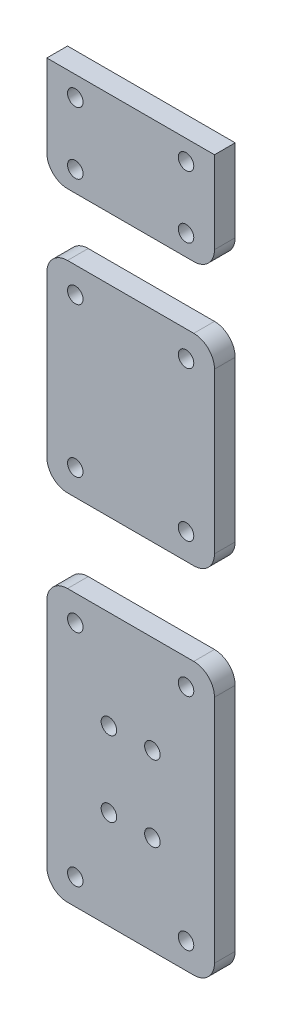
SolidWorks part; units mm, degrees
ref_plane "Front Plane" through (0, 0, 0) normal (0, 0, 1) x (1, 0, 0)
ref_plane "Top Plane" through (0, 0, 0) normal (0, 1, 0) x (1, 0, 0)
ref_plane "Right Plane" through (0, 0, 0) normal (1, 0, 0) x (0, 0, -1)
sketch "Sketch3" plane through (0, 0, 0) normal (0, 0, 1) x (1, 0, 0)
  line L0 (0, 94.0064) -> (0, 86.0614)
  line L1 (16.2, 94.0064) -> (16.2, 86.0614)
  line L2 (0, -0.1536) -> (16.2, -0.1536) construction
  line L3 (0, 76.0614) -> (0, 60.6064)
  line L4 (0, 94.0064) -> (16.2, 94.0064)
  line L5 (0, 12.3464) -> (4, 12.3464) construction
  line L6 (2, 58.6064) -> (4, 58.6064)
  line L7 (16.2, 76.0614) -> (16.2, 60.6064)
  line L8 (0, 48.6064) -> (0, 26.3464)
  line L9 (16.2, 48.6064) -> (16.2, 26.3464)
  line L10 (16.2, 12.3464) -> (16.2, -0.1536) construction
  line L11 (0, 12.3464) -> (0, -0.1536) construction
  line L12 (6, 12.3464) -> (6, 24.3464)
  line L13 (6, 24.3464) -> (10.2, 24.3464)
  line L14 (4, 12.3464) -> (4, 24.3464)
  line L15 (6, 12.3464) -> (10.2, 12.3464) construction
  line L16 (4, 50.6064) -> (4, 58.6064)
  line L17 (4, 78.0614) -> (4, 84.0614)
  line L18 (6, 50.6064) -> (6, 58.6064)
  line L19 (6, 78.0614) -> (6, 84.0614)
  line L20 (6, 84.0614) -> (10.2, 84.0614)
  line L21 (6, 78.0614) -> (10.2, 78.0614)
  line L22 (6, 58.6064) -> (10.2, 58.6064)
  line L23 (6, 50.6064) -> (10.2, 50.6064)
  line L24 (8.1, 94.0064) -> (8.1, -0.1536) construction
  line L25 (12.2, 50.6064) -> (12.2, 58.6064)
  line L26 (2, 50.6064) -> (4, 50.6064)
  line L27 (2, 24.3464) -> (4, 24.3464)
  line L28 (10.2, 12.3464) -> (10.2, 24.3464)
  line L29 (12.2, 12.3464) -> (12.2, 24.3464)
  line L30 (2, 78.0614) -> (4, 78.0614)
  line L31 (10.2, 50.6064) -> (10.2, 58.6064)
  line L32 (2, 84.0614) -> (4, 84.0614)
  line L33 (12.2, 78.0614) -> (12.2, 84.0614)
  line L34 (10.2, 78.0614) -> (10.2, 84.0614)
  line L35 (12.2, 84.0614) -> (14.2, 84.0614)
  line L36 (12.2, 78.0614) -> (14.2, 78.0614)
  line L37 (12.2, 58.6064) -> (14.2, 58.6064)
  line L38 (12.2, 50.6064) -> (14.2, 50.6064)
  line L39 (12.2, 12.3464) -> (16.2, 12.3464) construction
  line L40 (12.2, 24.3464) -> (14.2, 24.3464)
  line L41 (4, 12.3464) -> (6, 12.3464)
  line L42 (10.2, 12.3464) -> (12.2, 12.3464)
  circle A0 centre (6, 33.8464) radius 0.75
  circle A1 centre (10.2, 33.8464) radius 0.75
  circle A2 centre (2.75, 86.0614) radius 0.75
  circle A3 centre (10.2, 41.1664) radius 0.75
  circle A4 centre (13.45, 48.1064) radius 0.75
  circle A5 centre (2.75, 92.0614) radius 0.75
  circle A6 centre (13.45, 86.0614) radius 0.75
  circle A7 centre (2.75, 61.1064) radius 0.75
  arc A8 (14.2, 24.3464) -> (16.2, 26.3464) centre (14.2, 26.3464) ccw
  arc A9 (16.2, 48.6064) -> (14.2, 50.6064) centre (14.2, 48.6064) ccw
  arc A10 (2, 50.6064) -> (0, 48.6064) centre (2, 48.6064) ccw
  arc A11 (0, 26.3464) -> (2, 24.3464) centre (2, 26.3464) ccw
  arc A12 (0, 60.6064) -> (2, 58.6064) centre (2, 60.6064) ccw
  arc A13 (14.2, 58.6064) -> (16.2, 60.6064) centre (14.2, 60.6064) ccw
  arc A14 (16.2, 76.0614) -> (14.2, 78.0614) centre (14.2, 76.0614) ccw
  arc A15 (0, 76.0614) -> (2, 78.0614) centre (2, 76.0614) cw
  circle A16 centre (2.85, 9.8464) radius 0.75 construction
  circle A17 centre (13.35, 9.8464) radius 0.75 construction
  circle A18 centre (13.35, 3.8464) radius 0.75 construction
  circle A19 centre (2.85, 3.8464) radius 0.75 construction
  circle A20 centre (13.45, 61.1064) radius 0.75
  circle A21 centre (2.75, 75.5614) radius 0.75
  circle A22 centre (13.45, 26.8464) radius 0.75
  circle A23 centre (13.45, 75.5614) radius 0.75
  circle A24 centre (13.45, 92.0614) radius 0.75
  circle A25 centre (2.75, 26.8464) radius 0.75
  circle A26 centre (6, 41.1064) radius 0.75
  circle A27 centre (2.75, 48.1064) radius 0.75
  arc A28 (16.2, 86.0614) -> (14.2, 84.0614) centre (14.2, 86.0614) cw
  arc A29 (2, 84.0614) -> (0, 86.0614) centre (2, 86.0614) cw
  point P76 (16.2, 24.3464)
  point P80 (16.2, 50.6064)
  point P84 (0, 50.6064)
  point P88 (0, 24.3464)
  point P95 (0, 58.6064)
  point P99 (16.2, 58.6064)
  point P102 (16.2, 78.0614)
  point P105 (0, 78.0614)
  point P108 (16.2, 84.0614)
  point P111 (0, 84.0614)
  dimension "D1" = 2.5
  dimension "D2" = 9.5
  dimension "D32" = 6
  dimension "D33" = 6
  dimension "D49" = 1.5
  dimension "D50" = 2
  dimension "D3" = 2.5
  dimension "D4" = 9.5
  dimension "D5" = 6
  dimension "D6" = 2.75
  dimension "D7" = 2.75
  dimension "D8" = 6
  dimension "D9" = 2.5
  dimension "D10" = 2.5
  dimension "D11" = 9.5
  dimension "D12" = 9.44
  dimension "D13" = 2.75
  dimension "D14" = 6
  dimension "D15" = 2.75
  dimension "D16" = 6
  dimension "D17" = 12
  dimension "D18" = 2.5
  dimension "D19" = 4
  dimension "D20" = 6
  dimension "D21" = 6
  dimension "D22" = 4
  dimension "D23" = 2.85
  dimension "D24" = 2.85
  dimension "D25" = 26.26
  dimension "D26" = 16.2
  dimension "D27" = 8
  dimension "D28" = 2.5
  dimension "D29" = 2.5
  dimension "D30" = 2.75
  dimension "D31" = 2.75
  dimension "D34" = 2.5
  dimension "D35" = 2.5
  dimension "D36" = 2.75
  dimension "D37" = 2.75
  dimension "D38" = 19.455
  dimension "D39" = 6
  dimension "D40" = 2
  dimension "D41" = 2
  dimension "D42" = 2.75
  dimension "D43" = 2.75
  dimension "D44" = 2.5
  dimension "D45" = 4
  dimension "D46" = 2.75
  dimension "D47" = 2.75
  dimension "D48" = 9.945
extrude "Boss-Extrude3" add sketch "Sketch3" along normal blind 2
sketch "Sketch4" plane through (0, 0, 2) normal (0, 0, 1) x (1, 0, 0)
  line L0 (4, 84.0614) -> (12.2, 84.0614)
  line L1 (12.2, 84.0614) -> (12.2, 78.0614)
  line L2 (12.2, 78.0614) -> (4, 78.0614)
  line L3 (4, 78.0614) -> (4, 84.0614)
  line L4 (4, 58.6064) -> (12.2, 58.6064)
  line L5 (12.2, 58.6064) -> (12.2, 50.6064)
  line L6 (12.2, 50.6064) -> (4, 50.6064)
  line L7 (4, 50.6064) -> (4, 58.6064)
  line L8 (4, 24.3464) -> (12.2, 24.3464)
  line L9 (12.2, 24.3464) -> (12.2, 12.3464)
  line L10 (12.2, 12.3464) -> (4, 12.3464)
  line L11 (4, 12.3464) -> (4, 24.3464)
extrude "Cut-Extrude1" cut sketch "Sketch4" against normal up to surface (2 mm away) up to face at (2, 92.0614, 0)
equation "\"D25@Sketch3\"= \"HL@parametersSketch@prostheticParameters.SLDPRT\" * 0.196 - 4 - 6'Index PIP length"
equation "\"D26@Sketch3\"= \"fingerWidth@parametersSketch@prostheticParameters.SLDPRT\"'Index Width"
equation "\"D38@Sketch3\"= \"HL@parametersSketch@prostheticParameters.SLDPRT\" * 0.143 - 3 - 4 'Index MIP Length"
equation "\"D48@Sketch3\"= \"HL@parametersSketch@prostheticParameters.SLDPRT\" * 0.097 - 3 - 5'Index DIP Length - Gap Fingertip"
